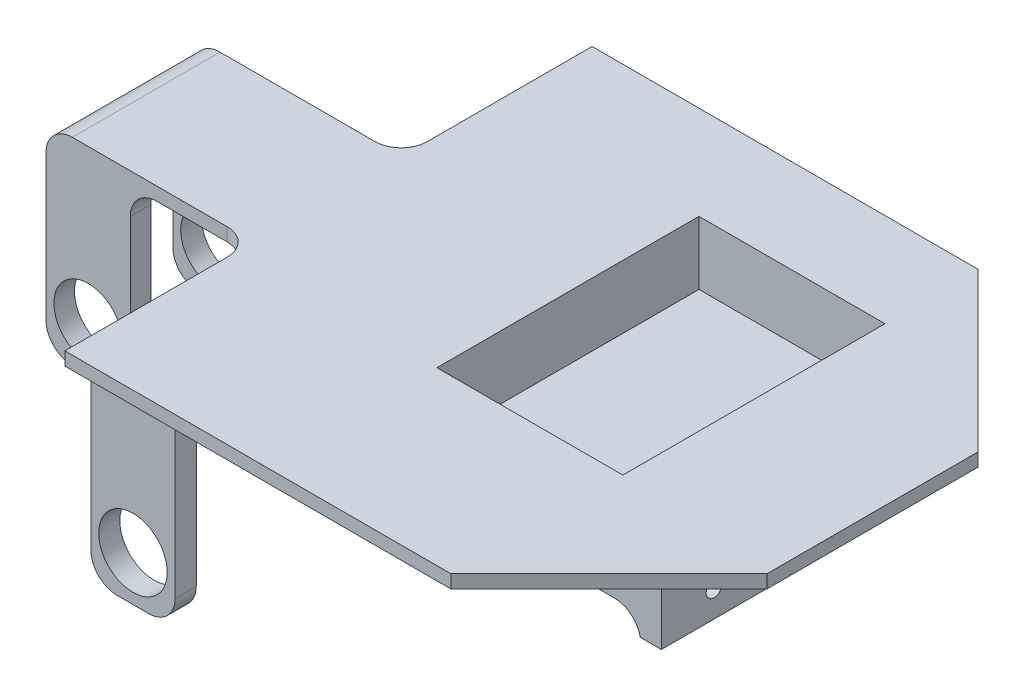
SolidWorks part; units mm, degrees
ref_plane "Front Plane" through (0, 0, 0) normal (0, 0, 1) x (1, 0, 0)
ref_plane "Top Plane" through (0, 0, 0) normal (0, 1, 0) x (1, 0, 0)
ref_plane "Right Plane" through (0, 0, 0) normal (1, 0, 0) x (0, 0, -1)
sketch "Sketch1" plane through (0, 0, 0) normal (0, 1, 0) x (1, 0, 0)
  line L1 (-100, -50) -> (100, -50)
  line L2 (-100, -50) -> (-100, 50)
  line L3 (-100, 50) -> (100, 50)
  line L4 (100, -50) -> (100, 50)
  line L5 (-100, -50) -> (100, 50) construction
  line L6 (-100, 50) -> (100, -50) construction
  point P0 (0, 0)
  dimension "D1" = 100
  dimension "D2" = 200
extrude "Boss-Extrude1" add sketch "Sketch1" along normal blind 2.5
sketch "Sketch2" plane through (0, 0, 0) normal (0, -1, 0) x (-1, 0, 0)
  line L0 (70.3794, -10.213) -> (80.3794, -10.213) construction
  line L1 (83.3794, 9.8365) -> (67.3794, 9.8365)
  line L2 (83.3794, 9.8365) -> (83.3794, 13.787)
  line L3 (83.3794, 13.787) -> (67.3794, 13.787)
  line L4 (67.3794, 9.8365) -> (67.3794, 13.787)
  line L5 (83.3794, -10.313) -> (67.3794, -10.313)
  line L6 (83.3794, -10.313) -> (83.3794, -14.213)
  line L7 (83.3794, -14.213) -> (67.3794, -14.213)
  line L8 (67.3794, -10.313) -> (67.3794, -14.213)
  line L9 (41.3794, 43.287) -> (25.3794, 43.287)
  line L10 (41.3794, 43.287) -> (41.3794, 47.287)
  line L11 (41.3794, 47.287) -> (25.3794, 47.287)
  line L12 (25.3794, 43.287) -> (25.3794, 47.287)
  line L13 (41.3794, -43.713) -> (25.3794, -43.713)
  line L14 (41.3794, -43.713) -> (41.3794, -47.713)
  line L15 (41.3794, -47.713) -> (25.3794, -47.713)
  line L16 (25.3794, -43.713) -> (25.3794, -47.713)
  line L17 (83.3794, 9.787) -> (67.3794, 9.787) construction
  line L19 (77.3794, 9.817) -> (77.3794, 21.787) construction
  line L20 (77.3794, -22.213) -> (77.3794, -10.243) construction
  line L21 (38.3794, 42.287) -> (28.3794, 42.287) construction
  line L22 (35.3794, 42.287) -> (35.3794, 47.287) construction
  line L23 (31.4169, -42.713) -> (32.3632, -42.713) construction
  line L24 (35.3794, -47.713) -> (35.3794, -42.713) construction
  point P20 (67.3794, 11.8117)
  dimension "D1" = 4
  dimension "D2" = 4
  dimension "D3" = 16
  dimension "D4" = 10
  dimension "D5" = 16
  dimension "D6" = 10
  dimension "D7" = 5
  dimension "D8" = 4
  dimension "D9" = 16
  dimension "D10" = 10
  dimension "D11" = 5
  dimension "D12" = 4
  dimension "D13" = 16
  dimension "D14" = 10
extrude "Boss-Extrude2" add sketch "Sketch2" along normal blind 35
sketch "Sketch3" plane through (0, 0, -13.787) normal (0, 0, -1) x (-1, 0, 0)
  circle A0 centre (33.3794, -26.4912) radius 6.5
  circle A1 centre (75.3794, -26.4912) radius 6.5
  dimension "D1" = 13
  dimension "D2" = 13
extrude "Cut-Extrude1" cut sketch "Sketch3" against normal blind 67 and the other way blind 39
sketch "Sketch4" plane through (0, 0, 0) normal (0, -1, 0) x (-1, 0, 0)
  line L0 (-100, 50) -> (100, 50) construction
  line L1 (44.0111, 50) -> (100, 50)
  line L2 (44.0111, 50) -> (44.0111, 13.787)
  line L3 (44.0111, 13.787) -> (83.3794, 13.787)
  line L4 (100, 50) -> (100, 13.787)
  line L5 (100, 50) -> (100, -50) construction
  line L6 (100, -50) -> (-100, -50) construction
  line L7 (44.0111, -50) -> (100, -50)
  line L8 (44.0111, -50) -> (44.0111, -14.213)
  line L9 (44.0111, -14.213) -> (83.3794, -14.213)
  line L10 (100, -50) -> (100, -14.213)
  line L13 (83.3794, 13.787) -> (83.3794, -14.213)
  line L15 (100, 13.787) -> (100, -14.213)
extrude "Cut-Extrude2" cut sketch "Sketch4" against normal blind 17
fillet "Fillet1" radius 5 8 edges at (-41.3794, -35, 45.713) (-25.3794, -35, 45.713) (-41.3794, -35, -45.287) (-25.3794, -35, -45.287) (-67.3794, -35, 12.263) (-83.3794, -35, 12.263) (-83.3794, -35, -11.8117) (-67.3794, -35, -11.8117)
sketch "Sketch5" plane through (0, 0, 0) normal (0, -1, 0) x (1, 0, 0)
  line L0 (-44.0111, 50) -> (100, 50) construction
  line L1 (100, -50) -> (59.1845, -50)
  line L2 (100, -50) -> (100, 50)
  line L3 (100, 50) -> (59.1845, 50)
  line L4 (59.1845, -50) -> (59.1845, 50)
extrude "Cut-Extrude3" cut sketch "Sketch5" against normal blind 17
fillet "Fillet2" radius 5 2 edges at (-44.0111, 1.25, 14.213) (-44.0111, 1.25, -13.787)
chamfer "Chamfer1" distance 30 angle 45 2 edges at (59.1845, 1.25, 50) (59.1845, 1.25, -50)
fillet "Fillet3" radius 5 1 edges at (-83.3794, 2.5, 0.213)
fillet "Fillet4" radius 5 2 edges at (-67.3794, 0, 12.263) (-67.3794, 0, -11.8117)
sketch "Sketch6" plane through (0, 0, 0) normal (0, -1, 0) x (1, 0, 0)
  line L1 (-8.1753, 19.9918) -> (39.1143, 19.9918)
  line L2 (-8.1753, 19.9918) -> (-8.1753, -35.0082)
  line L3 (-8.1753, -35.0082) -> (39.1143, -35.0082)
  line L4 (39.1143, 19.9918) -> (39.1143, -35.0082)
  dimension "D1" = 55
extrude "Boss-Extrude3" add sketch "Sketch6" along normal blind 20
sketch "Sketch7" plane through (0, 0, -35.0082) normal (0, 0, -1) x (-1, 0, 0)
  line L0 (8.1753, -20) -> (-39.1143, -20) construction
  line L1 (-35.1143, -20) -> (4.1753, -20)
  line L2 (-35.1143, -20) -> (-35.1143, -16)
  line L3 (-35.1143, -16) -> (4.1753, -16)
  line L4 (4.1753, -20) -> (4.1753, -16)
  line L5 (-39.1143, -20) -> (-39.1143, 0) construction
  line L6 (8.1753, -20) -> (8.1753, 0) construction
  dimension "D1" = 4
  dimension "D2" = 4
  dimension "D3" = 4
extrude "Cut-Extrude4" cut sketch "Sketch7" against normal blind 63
fillet "Fillet5" radius 5 2 edges at (-4.1753, -16, -7.5082) (35.1143, -16, -7.5082)
sketch "Sketch8" plane through (39.1143, 0, 0) normal (1, 0, 0) x (0, 0, -1)
  line L0 (-19.9918, -20) -> (-19.9918, 0) construction
  line L1 (35.0082, -20) -> (-19.9918, -20) construction
  circle A0 centre (-9.9918, -15) radius 1.5
  circle A1 centre (10.0082, -15) radius 1.5
  circle A2 centre (0.0082, -15) radius 1.5
  circle A3 centre (20.0082, -15) radius 1.5
  circle A4 centre (30.0082, -15) radius 1.5
  dimension "D1" = 3
  dimension "D2" = 3
  dimension "D3" = 3
  dimension "D10" = 3
  dimension "D11" = 3
  dimension "D4" = 10
  dimension "D5" = 10
  dimension "D6" = 10
  dimension "D7" = 5
  dimension "D8" = 5
  dimension "D9" = 5
  dimension "D12" = 10
  dimension "D13" = 10
extrude "Cut-Extrude5" cut sketch "Sketch8" against normal blind 63
sketch "Sketch9" plane through (0, 2.5, 0) normal (0, 1, 0) x (1, 0, 0)
  line L1 (29.3054, -17.4875) -> (-5.966, -17.4875)
  line L2 (29.3054, -17.4875) -> (29.3054, 32.2302)
  line L3 (29.3054, 32.2302) -> (-5.966, 32.2302)
  line L4 (-5.966, -17.4875) -> (-5.966, 32.2302)
extrude "Cut-Extrude6" cut sketch "Sketch9" against normal blind 12
